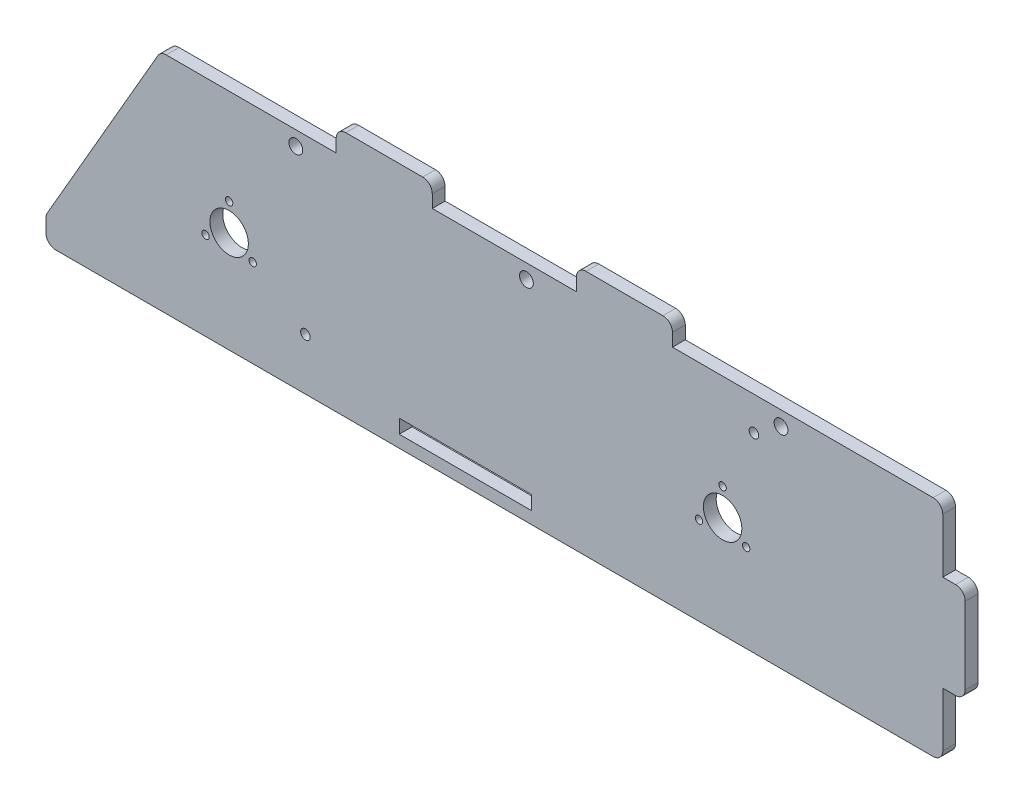
SolidWorks part; units mm, degrees
ref_plane "Front Plane" through (0, 0, 0) normal (0, 0, 1) x (1, 0, 0)
ref_plane "Top Plane" through (0, 0, 0) normal (0, 1, 0) x (1, 0, 0)
ref_plane "Right Plane" through (0, 0, 0) normal (1, 0, 0) x (0, 0, -1)
sketch "Sketch1" plane through (0, 0, 0) normal (0, 0, 1) x (1, 0, 0)
  line L0 (-128.1718, -30) -> (151.8282, -30)
  line L1 (-128.1718, -30) -> (-128.1718, -22)
  line L2 (-128.1718, -22) -> (-92.376, 40)
  line L5 (-37.566, 40) -> (-37.566, 47)
  line L6 (-37.566, 47) -> (-7.566, 47)
  line L7 (-7.566, 47) -> (-7.566, 40)
  line L8 (37.434, 40) -> (37.434, 47)
  line L9 (37.434, 47) -> (67.434, 47)
  line L10 (67.434, 47) -> (67.434, 40)
  line L11 (-92.376, 40) -> (-37.566, 40)
  line L12 (-7.566, 40) -> (37.434, 40)
  line L13 (67.434, 40) -> (151.8282, 40)
  line L16 (158.8282, 5) -> (158.8282, 20)
  line L17 (158.8282, 5) -> (158.8282, -10)
  line L18 (158.8282, -10) -> (151.8282, -10)
  line L19 (158.8282, 20) -> (151.8282, 20)
  line L20 (151.8282, 40) -> (151.8282, 20)
  line L21 (151.8282, -10) -> (151.8282, -30)
  line L22 (-17.8718, -21.85) -> (23.4282, -21.85)
  line L23 (-17.8718, -21.85) -> (-17.8718, -26.2)
  line L24 (-17.8718, -26.2) -> (23.4282, -26.2)
  line L25 (23.4282, -21.85) -> (23.4282, -26.2)
  circle A0 centre (-70.9918, 1.72) radius 6
  circle A3 centre (-70.9918, 1.72) radius 8.5 construction
  circle A4 centre (-70.9918, 10.22) radius 1.15
  circle A5 centre (-63.6305, -2.53) radius 1.15
  circle A6 centre (-78.353, -2.53) radius 1.15
  circle A7 centre (83.0882, 1.72) radius 6
  circle A8 centre (83.0882, 1.72) radius 8.5 construction
  circle A9 centre (83.0882, 10.22) radius 1.15
  circle A10 centre (90.4495, -2.53) radius 1.15
  circle A11 centre (75.727, -2.53) radius 1.15
  circle A12 centre (92.8604, 29.5) radius 1.5
  circle A13 centre (-50.1718, 35.5) radius 2.15
  circle A14 centre (21.8282, 35.5) radius 2.15
  circle A15 centre (101.3282, 35.5) radius 2.15
  circle A16 centre (-47.1718, -13.85) radius 1.5
  point P39 (151.8282, 30)
  dimension "D22" = 12
  dimension "D23" = 31.72
  dimension "D24" = 229.82
  dimension "D25" = 2.3
  dimension "D26" = 17
  dimension "D28" = 12
  dimension "D29" = 17
  dimension "D30" = 75.74
  dimension "D31" = 31.72
  dimension "D32" = 2.3
  dimension "D34" = 3
  dimension "D35" = 10.5
  dimension "D36" = 58.97
  dimension "D39" = 4.3
  dimension "D40" = 4.5
  dimension "D41" = 130
  dimension "D42" = 4.5
  dimension "D43" = 202
  dimension "D44" = 4.3
  dimension "D45" = 4.3
  dimension "D46" = 4.5
  dimension "D47" = 50.5
  dimension "D48" = 3
  dimension "D49" = 16.15
  dimension "D1" = 280
  dimension "D2" = 8
  dimension "D3" = 70
  dimension "D4" = 60
  dimension "D5" = 30
  dimension "D6" = 7
  dimension "D7" = 30
  dimension "D8" = 54.81
  dimension "D9" = 45
  dimension "D10" = 70
  dimension "D11" = 15
  dimension "D12" = 15
  dimension "D13" = 7
  dimension "D14" = 30
  dimension "D15" = 100
  dimension "D16" = 40
  dimension "D17" = 47
  dimension "D18" = 151.8282
  dimension "D19" = 20
  dimension "D20" = 41.3
  dimension "D21" = 4.35
  dimension "D37" = 3.8
  dimension "D38" = 110.3
  dimension "D50" = 199
  dimension "D27" = 3
  dimension "D33" = 3
extrude "Boss-Extrude1" add sketch "Sketch1" along normal blind 4
fillet "Fillet1" radius 3 11 edges at (-128.1718, -30, 2) (-128.1718, -22, 2) (-92.376, 40, 2) (-37.566, 47, 2) (-7.566, 47, 2) (37.434, 47, 2) (67.434, 47, 2) (151.8282, -30, 2) (158.8282, -10, 2) (158.8282, 20, 2) (151.8282, 40, 2)
